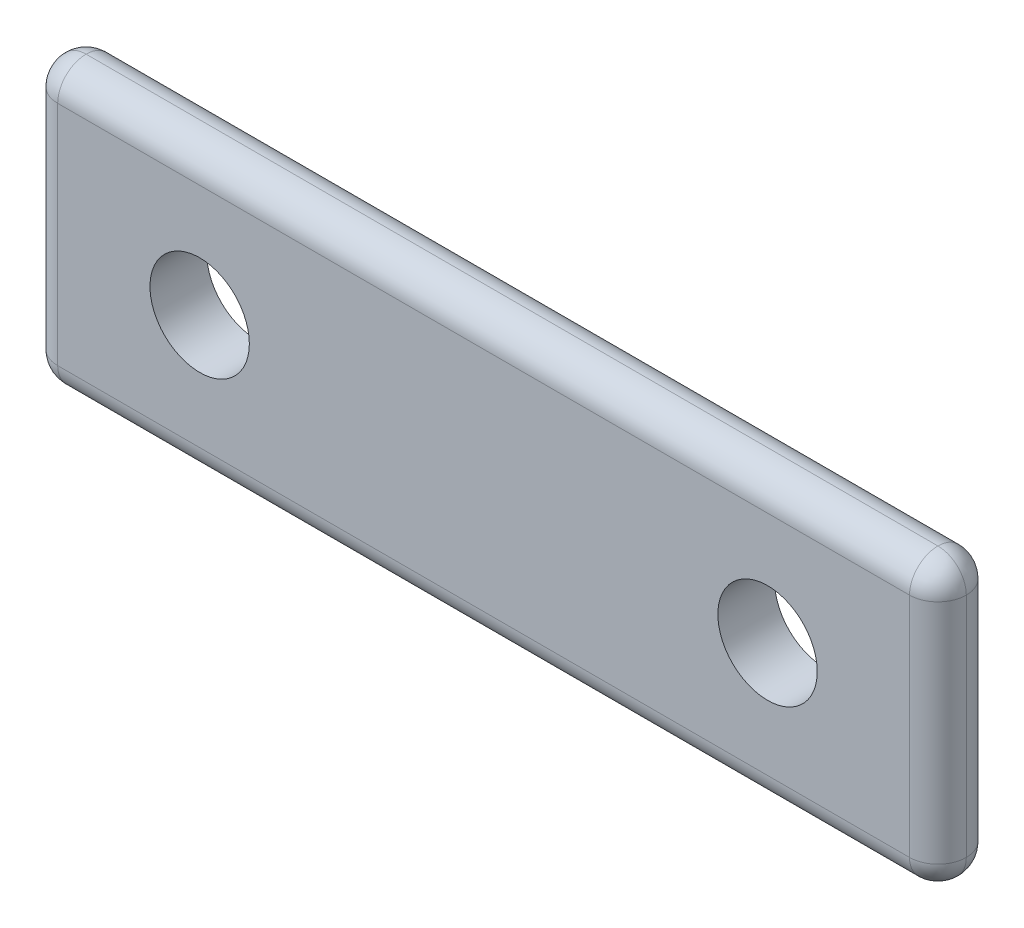
SolidWorks part; units mm, degrees
ref_plane "Plano frontal" through (0, 0, 0) normal (0, 0, 1) x (1, 0, 0)
ref_plane "Plano superior" through (0, 0, 0) normal (0, 1, 0) x (1, 0, 0)
ref_plane "Plano direito" through (0, 0, 0) normal (1, 0, 0) x (0, 0, -1)
sketch "Esboço1" plane through (0, 0, 0) normal (0, 0, 1) x (1, 0, 0)
  line L4 (0, 0) -> (0, 50)
  line L5 (0, 50) -> (160, 50)
  line L6 (160, 50) -> (160, 0)
  line L7 (160, 0) -> (0, 0)
  dimension "D1" = 160
  dimension "D2" = 50
extrude "Ressalto-extrusão1" add sketch "Esboço1" along normal blind 10
fillet "Filete1" radius 5 8 edges at (160, 25, 0) (160, 25, 10) (0, 25, 0) (0, 25, 10) (80, 0, 0) (80, 0, 10) (80, 50, 0) (80, 50, 10)
hole_wizard "Broca de rosquear para tarraxa de M201" positions "Esboço7" profile "Esboço8" hole size "M20" standard "DIN" end condition through all
sketch "Esboço7" plane through (0, 0, 10) normal (0, 0, 1) x (1, 0, 0)
  line L0 (0, 5) -> (0, 45) construction
  point P0 (30, 25.2069)
  point P2 (130, 25.2069)
  dimension "D1" = 100
  dimension "D2" = 30
sketch "Esboço8" plane through (30, 25.2069, 10) normal (1, 0, 0) x (0, -1, 0)
  line L0 (0, 0) -> (0, 10)
  line L1 (0, 10) -> (8.75, 10)
  line L2 (8.75, 10) -> (8.75, 0)
  line L5 (8.75, 0) -> (0, 0)
  line L11 (0, -6.35) -> (0, 107.95) construction
  dimension "Thru Hole Dia." = 17.5
  dimension "Thru Hole Depth" = 10
